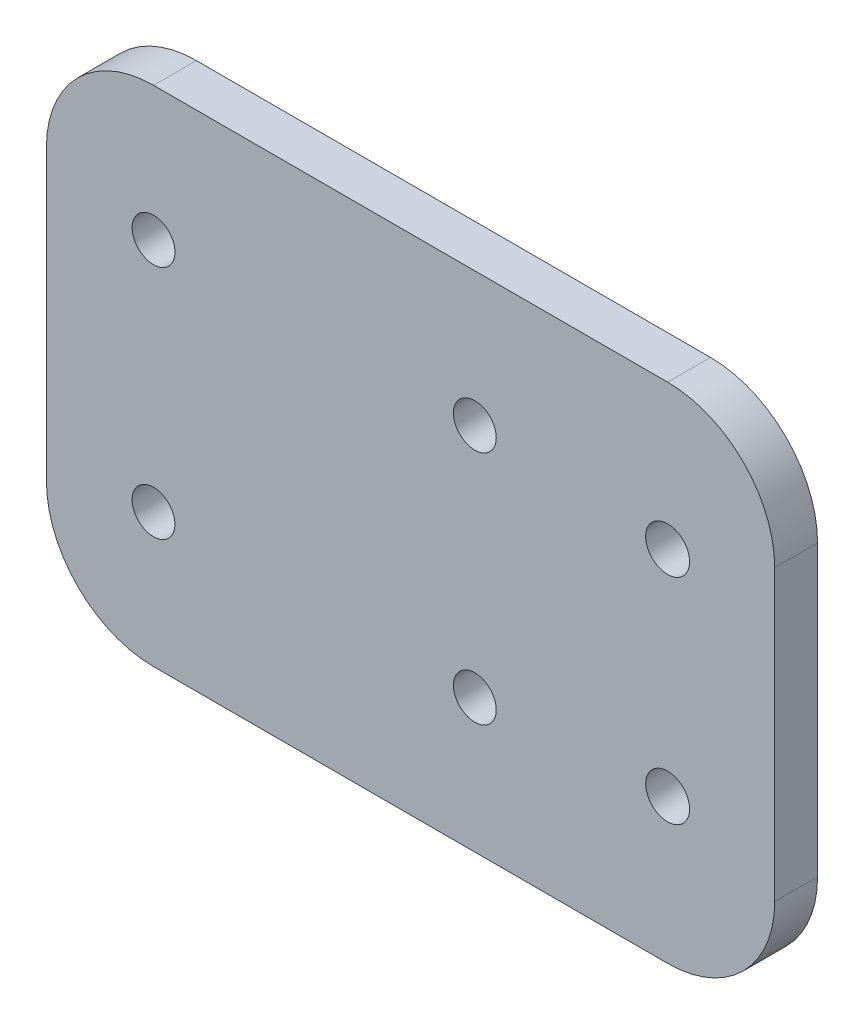
SolidWorks part; units mm, degrees
material "A-玻璃纤维"
ref_plane "前视基准面" through (0, 0, 0) normal (0, 0, 1) x (1, 0, 0)
ref_plane "上视基准面" through (0, 0, 0) normal (0, 1, 0) x (1, 0, 0)
ref_plane "右视基准面" through (0, 0, 0) normal (1, 0, 0) x (0, 0, -1)
other "Configuration Table"
sketch "草图1" plane through (0, 0, 0) normal (0, 0, 1) x (1, 0, 0)
  line L1 (0, 0) -> (68, 0)
  line L2 (0, 0) -> (0, 47)
  line L3 (0, 47) -> (68, 47)
  line L4 (68, 0) -> (68, 47)
  dimension "D1" = 68
  dimension "D2" = 47
extrude "凸台-拉伸1" add sketch "草图1" along normal blind 4
fillet "圆角1" radius 10 4 edges at (0, 47, 2) (68, 0, 2) (0, 0, 2) (68, 47, 2)
sketch "草图2" plane through (0, 0, 4) normal (0, 0, 1) x (1, 0, 0)
  line L0 (0, 37) -> (0, 10) construction
  line L1 (0, 23.5) -> (85.3311, 23.5) construction
  line L2 (30, 23.5) -> (115.3311, 23.5) construction
  line L3 (68, 10) -> (68, 37) construction
  circle A0 centre (10, 34.5) radius 2
  circle A1 centre (10, 12.5) radius 2
  circle A2 centre (40, 34.5) radius 2
  circle A3 centre (40, 12.5) radius 2
  circle A4 centre (58, 33.5) radius 2.05
  circle A5 centre (58, 13.5) radius 2.05
  dimension "D1" = 4
  dimension "D3" = 22
  dimension "D5" = 30
  dimension "D6" = 4.1
  dimension "D7" = 20
  dimension "D8" = 10
  dimension "D2" = 10
  dimension "D4" = 2
extrude "切除-拉伸1" cut sketch "草图2" against normal blind 4
